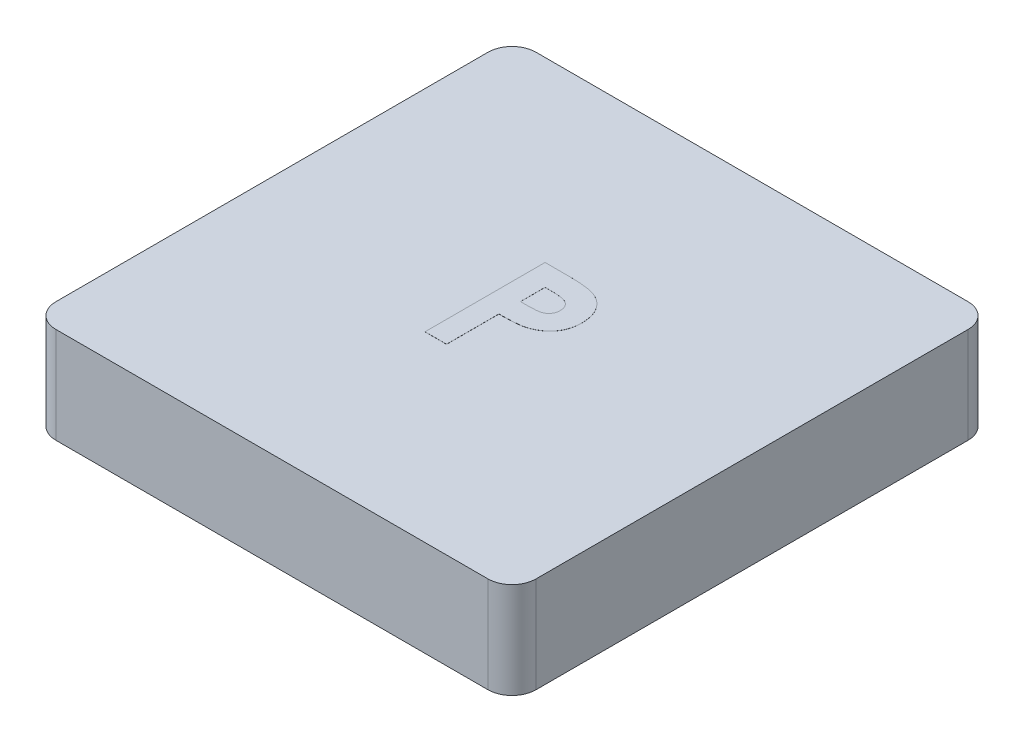
SolidWorks part; units mm, degrees
ref_plane "Front Plane" through (0, 0, 0) normal (0, 0, 1) x (1, 0, 0)
ref_plane "Top Plane" through (0, 0, 0) normal (0, 1, 0) x (1, 0, 0)
ref_plane "Right Plane" through (0, 0, 0) normal (1, 0, 0) x (0, 0, -1)
sketch "Sketch1" plane through (0, 0, 0) normal (0, 1, 0) x (1, 0, 0)
  line L0 (0, 0) -> (12.7, 0)
  line L1 (12.7, 0) -> (12.7, 12.7)
  line L2 (12.7, 12.7) -> (0, 12.7)
  line L3 (0, 12.7) -> (0, 0)
  dimension "D1" = 12.7
  dimension "D2" = 12.7
extrude "Boss-Extrude1" add sketch "Sketch1" along normal blind 2.54
fillet "Fillet1" radius 0.635 4 edges at (0, 1.27, -12.7) (12.7, 1.27, -12.7) (12.7, 1.27, 0) (0, 1.27, 0)
shell "Shell1" thickness 0.635 removed face at (6.35, 0, -6.35)
sketch "Sketch2" plane through (0, 1.905, 0) normal (0, -1, 0) x (-1, 0, 0)
  line L0 (-0.635, 6.35) -> (-12.065, 6.35) construction
  line L1 (-0.635, 12.065) -> (-0.635, 0.635) construction
  line L2 (-12.065, 0.635) -> (-12.065, 12.065) construction
  line L3 (-6.35, 0.635) -> (-6.35, 12.065) construction
  line L4 (-0.635, 0.635) -> (-12.065, 0.635) construction
  line L5 (-12.065, 12.065) -> (-0.635, 12.065) construction
  circle A0 centre (-6.35, 6.35) radius 2.54
  dimension "D1" = 5.08
extrude "Boss-Extrude2" add sketch "Sketch2" along normal up to surface (1.905 mm away) up to face at (6.35, 0, -6.35)
sketch "Sketch3" plane through (0, 2.54, 0) normal (0, 1, 0) x (1, 0, 0)
  line L0 (0, 12.065) -> (0, 0.635) construction
  line L1 (0.635, 0) -> (12.065, 0) construction
  text T0 "<b>P</b>"
  point P1 (0, 0)
  dimension "D1" = 5.207
  dimension "D2" = 4.826
extrude "Boss-Extrude3" add sketch "Sketch3" along normal blind 0.0025
